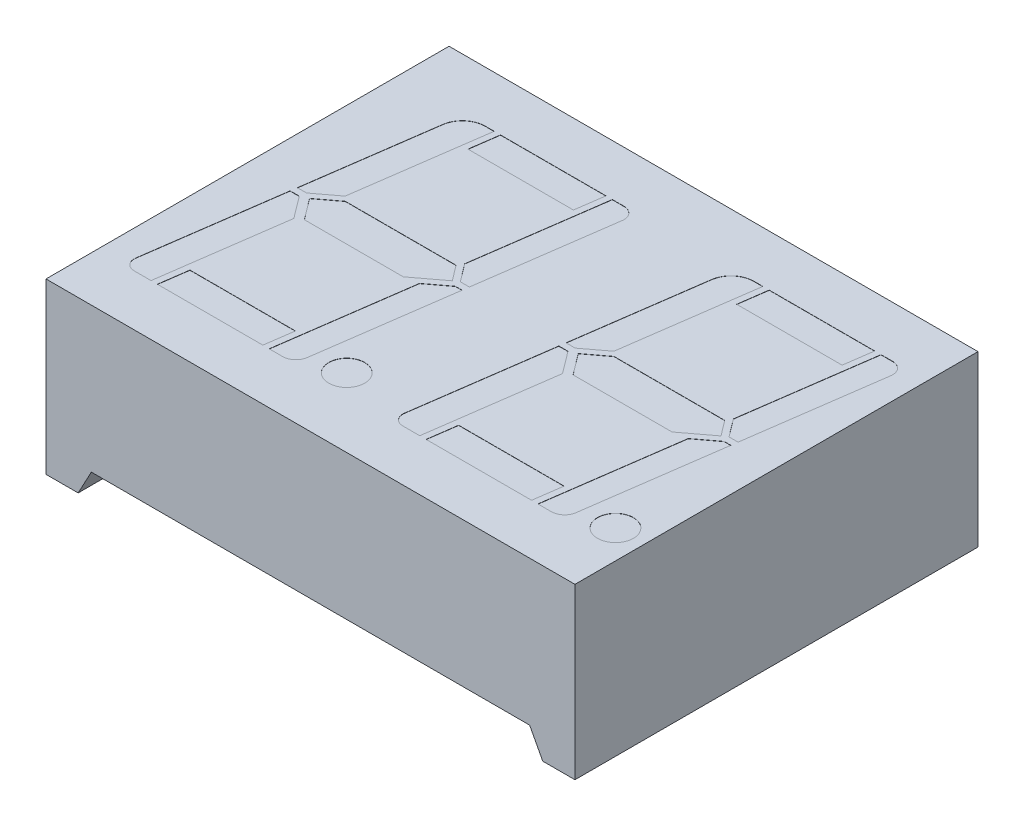
SolidWorks part; units mm, degrees
ref_plane "Front Plane" through (0, 0, 0) normal (0, 0, 1) x (1, 0, 0)
ref_plane "Top Plane" through (0, 0, 0) normal (0, 1, 0) x (1, 0, 0)
ref_plane "Right Plane" through (0, 0, 0) normal (1, 0, 0) x (0, 0, -1)
sketch "Sketch1" plane through (0, 0, 0) normal (0, 1, 0) x (1, 0, 0)
  line L1 (12.5, -9.525) -> (-12.5, -9.525)
  line L2 (12.5, -9.525) -> (12.5, 9.525)
  line L3 (12.5, 9.525) -> (-12.5, 9.525)
  line L4 (-12.5, -9.525) -> (-12.5, 9.525)
  line L5 (12.5, -9.525) -> (-12.5, 9.525) construction
  line L6 (12.5, 9.525) -> (-12.5, -9.525) construction
  point P0 (0, 0)
  dimension "D1" = 19.05
  dimension "D2" = 25
extrude "Boss-Extrude1" add sketch "Sketch1" along normal blind 8
sketch "Sketch2" plane through (0, 0, 9.525) normal (0, 0, 1) x (1, 0, 0)
  line L0 (-10.9796, 0) -> (-10.3577, 1.1654)
  line L1 (-12.5, 0) -> (12.5, 0) construction
  line L2 (-10.3577, 1.1654) -> (10.3577, 1.1654)
  line L3 (0, 0) -> (0, 8) construction
  line L4 (-12.5, 8) -> (12.5, 8) construction
  line L5 (10.9796, 0) -> (10.3577, 1.1654)
  point P12 (0, 1.1654)
  dimension "D1" = 1.5204
extrude "Cut-Extrude1" cut sketch "Sketch2" along direction (0, 0, 1) on the side against the normal through all
sketch "Sketch3" plane through (0, 8, 0) normal (0, 1, 0) x (1, 0, 0)
  line L0 (0, -9.525) -> (0, 9.525) construction
  line L1 (-12.5, -9.525) -> (12.5, -9.525) construction
  line L2 (12.5, 9.525) -> (-12.5, 9.525) construction
  line L3 (0, 0) -> (-12.5, 0) construction
  line L4 (-3.1842, -7.11) -> (0, -7.11) construction
  line L5 (-12.5, 9.525) -> (-12.5, -9.525) construction
  line L6 (-10.2939, 0.15) -> (-9.4466, 6.1791)
  line L7 (-11.3142, -7.11) -> (-3.1842, -7.11) construction
  line L8 (-11.3142, -7.11) -> (-9.3158, 7.11) construction
  line L9 (-9.3158, 7.11) -> (-1.1858, 7.11) construction
  line L10 (-3.1842, -7.11) -> (-1.1858, 7.11) construction
  line L11 (-11.3142, -7.11) -> (-1.1858, 7.11) construction
  line L12 (-9.3158, 7.11) -> (-3.1842, -7.11) construction
  line L13 (-7.9525, 7.11) -> (-8.8203, 0.9351)
  line L14 (-7.9525, 7.11) -> (-8.3757, 7.11)
  line L15 (-10.2939, 0.15) -> (-9.8622, 0.15)
  line L16 (-9.8622, 0.15) -> (-8.8203, 0.9351)
  line L17 (-6.25, 0.2145) -> (-6.25, 0.8985) construction
  line L18 (-2.3672, 7.11) -> (-1.8135, 7.11)
  line L19 (-7.6525, 7.11) -> (-2.6672, 7.11)
  line L20 (-7.6525, 7.11) -> (-7.8422, 5.76)
  line L21 (-7.8422, 5.76) -> (-2.8569, 5.76)
  line L22 (-2.6672, 7.11) -> (-2.8569, 5.76)
  line L23 (-1.2731, 6.4884) -> (-2.1639, 0.15)
  line L24 (-2.3672, 7.11) -> (-3.2272, 0.9904)
  line L25 (-3.2272, 0.9904) -> (-2.5939, 0.15)
  line L26 (-2.5939, 0.15) -> (-2.1639, 0.15)
  line L27 (-8.6046, 0.7266) -> (-3.37, 0.7266)
  line L28 (-8.6046, 0.7266) -> (-9.5688, 0)
  line L29 (-3.37, 0.7266) -> (-2.8225, 0)
  line L30 (-10.3361, -0.15) -> (-9.9043, -0.15)
  line L31 (-9.9043, -0.15) -> (-9.1192, -1.1919)
  line L32 (-9.1192, -1.1919) -> (-9.951, -7.11)
  line L33 (-9.951, -7.11) -> (-10.7505, -7.11)
  line L34 (-10.3361, -0.15) -> (-11.2358, -6.5517)
  line L35 (-9.8622, 0.15) -> (-9.756, 0.9057) construction
  line L36 (-2.8225, 0) -> (-4.1425, -0.9947)
  line L37 (-9.651, -7.11) -> (-4.6657, -7.11)
  line L38 (-9.651, -7.11) -> (-9.4612, -5.76)
  line L39 (-9.4612, -5.76) -> (-4.4759, -5.76)
  line L40 (-4.6657, -7.11) -> (-4.4759, -5.76)
  line L41 (-4.1425, -0.9947) -> (-8.8192, -0.9947)
  line L42 (-8.8192, -0.9947) -> (-9.5688, 0)
  line L43 (-2.2061, -0.15) -> (-3.1083, -6.5694)
  line L44 (-3.7302, -7.11) -> (-4.3657, -7.11)
  line L45 (-4.3657, -7.11) -> (-3.4899, -0.8786)
  line L46 (-3.4899, -0.8786) -> (-2.523, -0.15)
  line L47 (-2.523, -0.15) -> (-2.2061, -0.15)
  circle A0 centre (-1.55, -6.26) radius 0.85
  arc A1 (-9.4466, 6.1791) -> (-8.3757, 7.11) centre (-8.3757, 6.0286) cw
  arc A2 (-1.8135, 7.11) -> (-1.2731, 6.4884) centre (-1.8135, 6.5643) cw
  arc A3 (-11.2358, -6.5517) -> (-10.7505, -7.11) centre (-10.7505, -6.6199) ccw
  arc A4 (-3.7302, -7.11) -> (-3.1083, -6.5694) centre (-3.7302, -6.482) ccw
  point P12 (-6.25, 0)
  dimension "D1" = 4.7
  dimension "D2" = 14.22
  dimension "D3" = 8.13
  dimension "D4" = 1.35
  dimension "D5" = 8
  dimension "D6" = 135
  dimension "D7" = 0.4318
  dimension "D8" = 0.15
  dimension "D9" = 0.3
  dimension "D10" = 1.35
  dimension "D11" = 0.15
  dimension "D12" = 0.3
  dimension "D13" = 0.43
  dimension "D14" = 135
  dimension "D15" = 0.3
  dimension "D16" = 0.3
  dimension "D17" = 135
  dimension "D18" = 1.35
  dimension "D19" = 0.3
  dimension "D20" = 0.15
  dimension "D21" = 135
  dimension "D22" = 0.3
  dimension "D23" = 0.3
  dimension "D24" = 0.15
extrude "Cut-Extrude3" cut sketch "Sketch3" against normal blind 0.01
pattern_linear "LPattern2" [suppressed] count 2 spacing 12.7 of bodies 104
pattern_linear "LPattern3" count 2 spacing 12.7 along (1, 0, 0) of "Cut-Extrude3"
equation "\"D2@Sketch3\"  =14.22 /2"
equation "\"SegmentSpace\"=0.3"
equation "\"D8@Sketch3\"=\"SegmentSpace\" /2"
equation "\"D9@Sketch3\"=\"SegmentSpace\""
equation "\"SegmentWidth\"=1.35"
equation "\"D4@Sketch3\"=\"SegmentWidth\""
equation "\"D10@Sketch3\"=\"SegmentWidth\""
equation "\"D11@Sketch3\"=\"SegmentSpace\" /2"
equation "\"D12@Sketch3\"=\"SegmentSpace\""
equation "\"D15@Sketch3\"=\"SegmentSpace\""
equation "\"D16@Sketch3\"=\"SegmentSpace\""
equation "\"D18@Sketch3\"=\"SegmentWidth\""
equation "\"D19@Sketch3\"=\"SegmentSpace\""
equation "\"D20@Sketch3\"=\"SegmentSpace\" / 2"
equation "\"D22@Sketch3\"=\"SegmentSpace\""
equation "\"D23@Sketch3\"=\"SegmentSpace\""
equation "\"D24@Sketch3\"=\"SegmentSpace\" /2"
equation "\"D25@Sketch3\" = \"SegmentSpace\""
